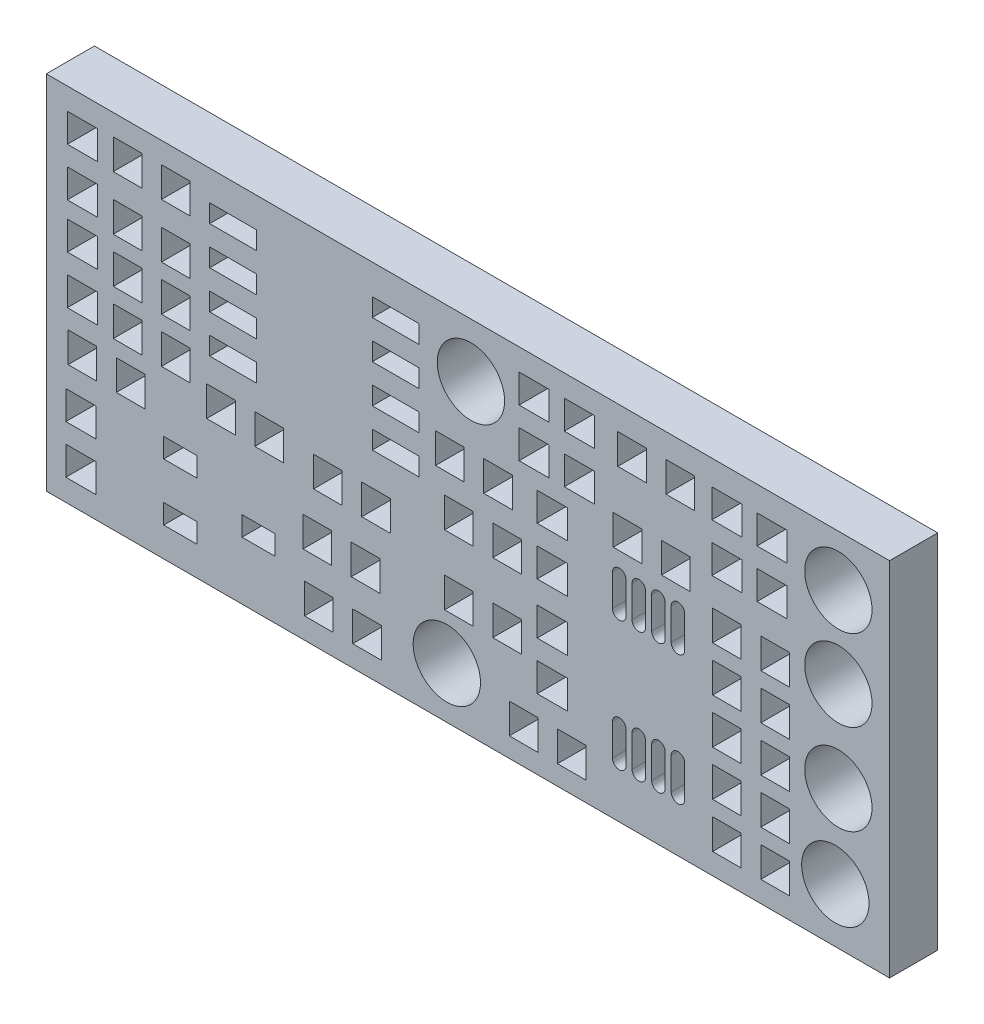
SolidWorks part; units mm, degrees
ref_plane "Plan de face" through (0, 0, 0) normal (0, 0, 1) x (1, 0, 0)
ref_plane "Plan de dessus" through (0, 0, 0) normal (0, 1, 0) x (1, 0, 0)
ref_plane "Plan de droite" through (0, 0, 0) normal (1, 0, 0) x (0, 0, -1)
sketch "Model" plane through (0, 0, 0) normal (0, 0, 1) x (1, 0, 0)
  line L0 (3.9, 2.875) -> (3.9, 3.525)
  line L1 (3.9, 3.525) -> (5, 3.525)
  line L2 (5, 3.525) -> (5, 2.875)
  line L3 (5, 2.875) -> (3.9, 2.875)
  line L4 (3.9, 0.975) -> (3.9, 1.625)
  line L5 (3.9, 1.625) -> (5, 1.625)
  line L6 (5, 1.625) -> (5, 0.975)
  line L7 (5, 0.975) -> (3.9, 0.975)
  line L8 (6.5, 1.925) -> (6.5, 2.575)
  line L9 (6.5, 2.575) -> (7.6, 2.575)
  line L10 (7.6, 2.575) -> (7.6, 1.925)
  line L11 (7.6, 1.925) -> (6.5, 1.925)
  line L12 (19.25, 2.775) -> (19.25, 1.725)
  line L13 (18.8, 1.725) -> (18.8, 2.775)
  line L14 (19.9, 2.775) -> (19.9, 1.725)
  line L15 (19.45, 1.725) -> (19.45, 2.775)
  line L16 (20.55, 2.775) -> (20.55, 1.725)
  line L17 (20.1, 1.725) -> (20.1, 2.775)
  line L18 (21.2, 2.775) -> (21.2, 1.725)
  line L19 (20.75, 1.725) -> (20.75, 2.775)
  line L20 (21.2, 7.075) -> (21.2, 6.025)
  line L21 (20.75, 6.025) -> (20.75, 7.075)
  line L22 (20.55, 7.075) -> (20.55, 6.025)
  line L23 (20.1, 6.025) -> (20.1, 7.075)
  line L24 (19.9, 7.075) -> (19.9, 6.025)
  line L25 (19.45, 6.025) -> (19.45, 7.075)
  line L26 (19.25, 7.075) -> (19.25, 6.025)
  line L27 (18.8, 6.025) -> (18.8, 7.075)
  line L28 (12.375, 7.195) -> (12.375, 6.595)
  line L29 (12.375, 6.595) -> (10.825, 6.595)
  line L30 (10.825, 6.595) -> (10.825, 7.195)
  line L31 (10.825, 7.195) -> (12.375, 7.195)
  line L32 (12.375, 8.465) -> (12.375, 7.865)
  line L33 (12.375, 7.865) -> (10.825, 7.865)
  line L34 (10.825, 7.865) -> (10.825, 8.465)
  line L35 (10.825, 8.465) -> (12.375, 8.465)
  line L36 (12.375, 9.735) -> (12.375, 9.135)
  line L37 (12.375, 9.135) -> (10.825, 9.135)
  line L38 (10.825, 9.135) -> (10.825, 9.735)
  line L39 (10.825, 9.735) -> (12.375, 9.735)
  line L40 (12.375, 11.005) -> (12.375, 10.405)
  line L41 (12.375, 10.405) -> (10.825, 10.405)
  line L42 (10.825, 10.405) -> (10.825, 11.005)
  line L43 (10.825, 11.005) -> (12.375, 11.005)
  line L44 (6.975, 11.005) -> (6.975, 10.405)
  line L45 (6.975, 10.405) -> (5.425, 10.405)
  line L46 (5.425, 10.405) -> (5.425, 11.005)
  line L47 (5.425, 11.005) -> (6.975, 11.005)
  line L48 (6.975, 9.735) -> (6.975, 9.135)
  line L49 (6.975, 9.135) -> (5.425, 9.135)
  line L50 (5.425, 9.135) -> (5.425, 9.735)
  line L51 (5.425, 9.735) -> (6.975, 9.735)
  line L52 (6.975, 8.465) -> (6.975, 7.865)
  line L53 (6.975, 7.865) -> (5.425, 7.865)
  line L54 (5.425, 7.865) -> (5.425, 8.465)
  line L55 (5.425, 8.465) -> (6.975, 8.465)
  line L56 (6.975, 7.195) -> (6.975, 6.595)
  line L57 (6.975, 6.595) -> (5.425, 6.595)
  line L58 (5.425, 6.595) -> (5.425, 7.195)
  line L59 (5.425, 7.195) -> (6.975, 7.195)
  line L60 (20.575, 11.2) -> (21.525, 11.2)
  line L61 (21.525, 11.2) -> (21.525, 10.2)
  line L62 (21.525, 10.2) -> (20.575, 10.2)
  line L63 (20.575, 10.2) -> (20.575, 11.2)
  line L64 (18.975, 11.2) -> (19.925, 11.2)
  line L65 (19.925, 11.2) -> (19.925, 10.2)
  line L66 (19.925, 10.2) -> (18.975, 10.2)
  line L67 (18.975, 10.2) -> (18.975, 11.2)
  line L68 (23.075, 5.2) -> (22.125, 5.2)
  line L69 (22.125, 5.2) -> (22.125, 6.2)
  line L70 (22.125, 6.2) -> (23.075, 6.2)
  line L71 (23.075, 6.2) -> (23.075, 5.2)
  line L72 (24.675, 5.2) -> (23.725, 5.2)
  line L73 (23.725, 5.2) -> (23.725, 6.2)
  line L74 (23.725, 6.2) -> (24.675, 6.2)
  line L75 (24.675, 6.2) -> (24.675, 5.2)
  line L76 (16.325, 0.65) -> (15.375, 0.65)
  line L77 (15.375, 0.65) -> (15.375, 1.65)
  line L78 (15.375, 1.65) -> (16.325, 1.65)
  line L79 (16.325, 1.65) -> (16.325, 0.65)
  line L80 (17.925, 0.65) -> (16.975, 0.65)
  line L81 (16.975, 0.65) -> (16.975, 1.65)
  line L82 (16.975, 1.65) -> (17.925, 1.65)
  line L83 (17.925, 1.65) -> (17.925, 0.65)
  line L84 (17.3, 6.575) -> (17.3, 5.625)
  line L85 (17.3, 5.625) -> (16.3, 5.625)
  line L86 (16.3, 5.625) -> (16.3, 6.575)
  line L87 (16.3, 6.575) -> (17.3, 6.575)
  line L88 (17.3, 8.175) -> (17.3, 7.225)
  line L89 (17.3, 7.225) -> (16.3, 7.225)
  line L90 (16.3, 7.225) -> (16.3, 8.175)
  line L91 (16.3, 8.175) -> (17.3, 8.175)
  line L92 (16.3, 3.925) -> (16.3, 4.875)
  line L93 (16.3, 4.875) -> (17.3, 4.875)
  line L94 (17.3, 4.875) -> (17.3, 3.925)
  line L95 (17.3, 3.925) -> (16.3, 3.925)
  line L96 (16.3, 2.325) -> (16.3, 3.275)
  line L97 (16.3, 3.275) -> (17.3, 3.275)
  line L98 (17.3, 3.275) -> (17.3, 2.325)
  line L99 (17.3, 2.325) -> (16.3, 2.325)
  line L100 (19.775, 7.8) -> (18.825, 7.8)
  line L101 (18.825, 7.8) -> (18.825, 8.8)
  line L102 (18.825, 8.8) -> (19.775, 8.8)
  line L103 (19.775, 8.8) -> (19.775, 7.8)
  line L104 (21.375, 7.8) -> (20.425, 7.8)
  line L105 (20.425, 7.8) -> (20.425, 8.8)
  line L106 (20.425, 8.8) -> (21.375, 8.8)
  line L107 (21.375, 8.8) -> (21.375, 7.8)
  line L108 (23.725, 7.7) -> (24.675, 7.7)
  line L109 (24.675, 7.7) -> (24.675, 6.7)
  line L110 (24.675, 6.7) -> (23.725, 6.7)
  line L111 (23.725, 6.7) -> (23.725, 7.7)
  line L112 (22.125, 7.7) -> (23.075, 7.7)
  line L113 (23.075, 7.7) -> (23.075, 6.7)
  line L114 (23.075, 6.7) -> (22.125, 6.7)
  line L115 (22.125, 6.7) -> (22.125, 7.7)
  line L116 (14.825, 6.5) -> (15.775, 6.5)
  line L117 (15.775, 6.5) -> (15.775, 5.5)
  line L118 (15.775, 5.5) -> (14.825, 5.5)
  line L119 (14.825, 5.5) -> (14.825, 6.5)
  line L120 (13.225, 6.5) -> (14.175, 6.5)
  line L121 (14.175, 6.5) -> (14.175, 5.5)
  line L122 (14.175, 5.5) -> (13.225, 5.5)
  line L123 (13.225, 5.5) -> (13.225, 6.5)
  line L124 (14.825, 4.2) -> (15.775, 4.2)
  line L125 (15.775, 4.2) -> (15.775, 3.2)
  line L126 (15.775, 3.2) -> (14.825, 3.2)
  line L127 (14.825, 3.2) -> (14.825, 4.2)
  line L128 (13.225, 4.2) -> (14.175, 4.2)
  line L129 (14.175, 4.2) -> (14.175, 3.2)
  line L130 (14.175, 3.2) -> (13.225, 3.2)
  line L131 (13.225, 3.2) -> (13.225, 4.2)
  line L132 (23.075, 3.7) -> (22.125, 3.7)
  line L133 (22.125, 3.7) -> (22.125, 4.7)
  line L134 (22.125, 4.7) -> (23.075, 4.7)
  line L135 (23.075, 4.7) -> (23.075, 3.7)
  line L136 (24.675, 3.7) -> (23.725, 3.7)
  line L137 (23.725, 3.7) -> (23.725, 4.7)
  line L138 (23.725, 4.7) -> (24.675, 4.7)
  line L139 (24.675, 4.7) -> (24.675, 3.7)
  line L140 (23.075, 2.2) -> (22.125, 2.2)
  line L141 (22.125, 2.2) -> (22.125, 3.2)
  line L142 (22.125, 3.2) -> (23.075, 3.2)
  line L143 (23.075, 3.2) -> (23.075, 2.2)
  line L144 (24.675, 2.2) -> (23.725, 2.2)
  line L145 (23.725, 2.2) -> (23.725, 3.2)
  line L146 (23.725, 3.2) -> (24.675, 3.2)
  line L147 (24.675, 3.2) -> (24.675, 2.2)
  line L148 (23.725, 1.7) -> (24.675, 1.7)
  line L149 (24.675, 1.7) -> (24.675, 0.7)
  line L150 (24.675, 0.7) -> (23.725, 0.7)
  line L151 (23.725, 0.7) -> (23.725, 1.7)
  line L152 (22.125, 1.7) -> (23.075, 1.7)
  line L153 (23.075, 1.7) -> (23.075, 0.7)
  line L154 (23.075, 0.7) -> (22.125, 0.7)
  line L155 (22.125, 0.7) -> (22.125, 1.7)
  line L156 (18.2, 9.675) -> (18.2, 8.725)
  line L157 (18.2, 8.725) -> (17.2, 8.725)
  line L158 (17.2, 8.725) -> (17.2, 9.675)
  line L159 (17.2, 9.675) -> (18.2, 9.675)
  line L160 (18.2, 11.275) -> (18.2, 10.325)
  line L161 (18.2, 10.325) -> (17.2, 10.325)
  line L162 (17.2, 10.325) -> (17.2, 11.275)
  line L163 (17.2, 11.275) -> (18.2, 11.275)
  line L164 (23.1, 9.575) -> (23.1, 8.625)
  line L165 (23.1, 8.625) -> (22.1, 8.625)
  line L166 (22.1, 8.625) -> (22.1, 9.575)
  line L167 (22.1, 9.575) -> (23.1, 9.575)
  line L168 (23.1, 11.175) -> (23.1, 10.225)
  line L169 (23.1, 10.225) -> (22.1, 10.225)
  line L170 (22.1, 10.225) -> (22.1, 11.175)
  line L171 (22.1, 11.175) -> (23.1, 11.175)
  line L172 (23.6, 10.225) -> (23.6, 11.175)
  line L173 (23.6, 11.175) -> (24.6, 11.175)
  line L174 (24.6, 11.175) -> (24.6, 10.225)
  line L175 (24.6, 10.225) -> (23.6, 10.225)
  line L176 (23.6, 8.625) -> (23.6, 9.575)
  line L177 (23.6, 9.575) -> (24.6, 9.575)
  line L178 (24.6, 9.575) -> (24.6, 8.625)
  line L179 (24.6, 8.625) -> (23.6, 8.625)
  line L180 (1.7, 9.675) -> (1.7, 8.725)
  line L181 (1.7, 8.725) -> (0.7, 8.725)
  line L182 (0.7, 8.725) -> (0.7, 9.675)
  line L183 (0.7, 9.675) -> (1.7, 9.675)
  line L184 (1.7, 11.275) -> (1.7, 10.325)
  line L185 (1.7, 10.325) -> (0.7, 10.325)
  line L186 (0.7, 10.325) -> (0.7, 11.275)
  line L187 (0.7, 11.275) -> (1.7, 11.275)
  line L188 (15.7, 10.325) -> (15.7, 11.275)
  line L189 (15.7, 11.275) -> (16.7, 11.275)
  line L190 (16.7, 11.275) -> (16.7, 10.325)
  line L191 (16.7, 10.325) -> (15.7, 10.325)
  line L192 (15.7, 8.725) -> (15.7, 9.675)
  line L193 (15.7, 9.675) -> (16.7, 9.675)
  line L194 (16.7, 9.675) -> (16.7, 8.725)
  line L195 (16.7, 8.725) -> (15.7, 8.725)
  line L196 (0.7, 7.225) -> (0.7, 8.175)
  line L197 (0.7, 8.175) -> (1.7, 8.175)
  line L198 (1.7, 8.175) -> (1.7, 7.225)
  line L199 (1.7, 7.225) -> (0.7, 7.225)
  line L200 (0.7, 5.625) -> (0.7, 6.575)
  line L201 (0.7, 6.575) -> (1.7, 6.575)
  line L202 (1.7, 6.575) -> (1.7, 5.625)
  line L203 (1.7, 5.625) -> (0.7, 5.625)
  line L204 (10.175, 1.7) -> (11.125, 1.7)
  line L205 (11.125, 1.7) -> (11.125, 0.7)
  line L206 (11.125, 0.7) -> (10.175, 0.7)
  line L207 (10.175, 0.7) -> (10.175, 1.7)
  line L208 (8.575, 1.7) -> (9.525, 1.7)
  line L209 (9.525, 1.7) -> (9.525, 0.7)
  line L210 (9.525, 0.7) -> (8.575, 0.7)
  line L211 (8.575, 0.7) -> (8.575, 1.7)
  line L212 (3.825, 11.3) -> (4.775, 11.3)
  line L213 (4.775, 11.3) -> (4.775, 10.3)
  line L214 (4.775, 10.3) -> (3.825, 10.3)
  line L215 (3.825, 10.3) -> (3.825, 11.3)
  line L216 (2.225, 11.3) -> (3.175, 11.3)
  line L217 (3.175, 11.3) -> (3.175, 10.3)
  line L218 (3.175, 10.3) -> (2.225, 10.3)
  line L219 (2.225, 10.3) -> (2.225, 11.3)
  line L220 (1.65, 1.675) -> (1.65, 0.725)
  line L221 (1.65, 0.725) -> (0.65, 0.725)
  line L222 (0.65, 0.725) -> (0.65, 1.675)
  line L223 (0.65, 1.675) -> (1.65, 1.675)
  line L224 (1.65, 3.275) -> (1.65, 2.325)
  line L225 (1.65, 2.325) -> (0.65, 2.325)
  line L226 (0.65, 2.325) -> (0.65, 3.275)
  line L227 (0.65, 3.275) -> (1.65, 3.275)
  line L228 (14.525, 8.2) -> (15.475, 8.2)
  line L229 (15.475, 8.2) -> (15.475, 7.2)
  line L230 (15.475, 7.2) -> (14.525, 7.2)
  line L231 (14.525, 7.2) -> (14.525, 8.2)
  line L232 (12.925, 8.2) -> (13.875, 8.2)
  line L233 (13.875, 8.2) -> (13.875, 7.2)
  line L234 (13.875, 7.2) -> (12.925, 7.2)
  line L235 (12.925, 7.2) -> (12.925, 8.2)
  line L236 (6.275, 4.75) -> (5.325, 4.75)
  line L237 (5.325, 4.75) -> (5.325, 5.75)
  line L238 (5.325, 5.75) -> (6.275, 5.75)
  line L239 (6.275, 5.75) -> (6.275, 4.75)
  line L240 (7.875, 4.75) -> (6.925, 4.75)
  line L241 (6.925, 4.75) -> (6.925, 5.75)
  line L242 (6.925, 5.75) -> (7.875, 5.75)
  line L243 (7.875, 5.75) -> (7.875, 4.75)
  line L244 (2.325, 5) -> (3.275, 5)
  line L245 (3.275, 5) -> (3.275, 4)
  line L246 (3.275, 4) -> (2.325, 4)
  line L247 (2.325, 4) -> (2.325, 5)
  line L248 (0.725, 5) -> (1.675, 5)
  line L249 (1.675, 5) -> (1.675, 4)
  line L250 (1.675, 4) -> (0.725, 4)
  line L251 (0.725, 4) -> (0.725, 5)
  line L252 (10.125, 3.6) -> (11.075, 3.6)
  line L253 (11.075, 3.6) -> (11.075, 2.6)
  line L254 (11.075, 2.6) -> (10.125, 2.6)
  line L255 (10.125, 2.6) -> (10.125, 3.6)
  line L256 (8.525, 3.6) -> (9.475, 3.6)
  line L257 (9.475, 3.6) -> (9.475, 2.6)
  line L258 (9.475, 2.6) -> (8.525, 2.6)
  line L259 (8.525, 2.6) -> (8.525, 3.6)
  line L260 (9.825, 4.5) -> (8.875, 4.5)
  line L261 (8.875, 4.5) -> (8.875, 5.5)
  line L262 (8.875, 5.5) -> (9.825, 5.5)
  line L263 (9.825, 5.5) -> (9.825, 4.5)
  line L264 (11.425, 4.5) -> (10.475, 4.5)
  line L265 (10.475, 4.5) -> (10.475, 5.5)
  line L266 (10.475, 5.5) -> (11.425, 5.5)
  line L267 (11.425, 5.5) -> (11.425, 4.5)
  line L268 (3.175, 7) -> (2.225, 7)
  line L269 (2.225, 7) -> (2.225, 8)
  line L270 (2.225, 8) -> (3.175, 8)
  line L271 (3.175, 8) -> (3.175, 7)
  line L272 (4.775, 7) -> (3.825, 7)
  line L273 (3.825, 7) -> (3.825, 8)
  line L274 (3.825, 8) -> (4.775, 8)
  line L275 (4.775, 8) -> (4.775, 7)
  line L276 (3.175, 8.5) -> (2.225, 8.5)
  line L277 (2.225, 8.5) -> (2.225, 9.5)
  line L278 (2.225, 9.5) -> (3.175, 9.5)
  line L279 (3.175, 9.5) -> (3.175, 8.5)
  line L280 (4.775, 8.5) -> (3.825, 8.5)
  line L281 (3.825, 8.5) -> (3.825, 9.5)
  line L282 (3.825, 9.5) -> (4.775, 9.5)
  line L283 (4.775, 9.5) -> (4.775, 8.5)
  line L284 (3.825, 6.5) -> (4.775, 6.5)
  line L285 (4.775, 6.5) -> (4.775, 5.5)
  line L286 (4.775, 5.5) -> (3.825, 5.5)
  line L287 (3.825, 5.5) -> (3.825, 6.5)
  line L288 (2.225, 6.5) -> (3.175, 6.5)
  line L289 (3.175, 6.5) -> (3.175, 5.5)
  line L290 (3.175, 5.5) -> (2.225, 5.5)
  line L291 (2.225, 5.5) -> (2.225, 6.5)
  line L292 (0, 0) -> (0, 12)
  line L293 (0, 12) -> (28, 12)
  line L294 (28, 12) -> (28, 0)
  line L295 (28, 0) -> (0, 0)
  circle A0 centre (26.3, 10.3) radius 1.1176
  circle A1 centre (26.3, 10.3) radius 1.1176
  circle A2 centre (26.3, 7.6) radius 1.1176
  circle A3 centre (26.3, 7.6) radius 1.1176
  circle A4 centre (26.2, 1.8) radius 1.1176
  circle A5 centre (26.2, 1.8) radius 1.1176
  circle A6 centre (26.3, 4.6) radius 1.1176
  circle A7 centre (26.3, 4.6) radius 1.1176
  circle A8 centre (13.3, 1.7) radius 1.1176
  circle A9 centre (13.3, 1.7) radius 1.1176
  circle A10 centre (14.1, 10.2) radius 1.1176
  circle A11 centre (14.1, 10.2) radius 1.1176
  arc A12 (18.8, 1.725) -> (19.25, 1.725) centre (19.025, 1.725) ccw
  arc A13 (19.25, 2.775) -> (18.8, 2.775) centre (19.025, 2.775) ccw
  arc A14 (19.45, 1.725) -> (19.9, 1.725) centre (19.675, 1.725) ccw
  arc A15 (19.9, 2.775) -> (19.45, 2.775) centre (19.675, 2.775) ccw
  arc A16 (20.1, 1.725) -> (20.55, 1.725) centre (20.325, 1.725) ccw
  arc A17 (20.55, 2.775) -> (20.1, 2.775) centre (20.325, 2.775) ccw
  arc A18 (20.75, 1.725) -> (21.2, 1.725) centre (20.975, 1.725) ccw
  arc A19 (21.2, 2.775) -> (20.75, 2.775) centre (20.975, 2.775) ccw
  arc A20 (20.75, 6.025) -> (21.2, 6.025) centre (20.975, 6.025) ccw
  arc A21 (21.2, 7.075) -> (20.75, 7.075) centre (20.975, 7.075) ccw
  arc A22 (20.1, 6.025) -> (20.55, 6.025) centre (20.325, 6.025) ccw
  arc A23 (20.55, 7.075) -> (20.1, 7.075) centre (20.325, 7.075) ccw
  arc A24 (19.45, 6.025) -> (19.9, 6.025) centre (19.675, 6.025) ccw
  arc A25 (19.9, 7.075) -> (19.45, 7.075) centre (19.675, 7.075) ccw
  arc A26 (18.8, 6.025) -> (19.25, 6.025) centre (19.025, 6.025) ccw
  arc A27 (19.25, 7.075) -> (18.8, 7.075) centre (19.025, 7.075) ccw
extrude "Boss.-Extru.1" add sketch "Model" along normal blind 1.6 contours L295 L294 L293 L292 A27 L26 A26 L27 A25 L24 A24 L25 A23 L22 A22 L23 A21 L20 A20 L21 A19 L18 A18 L19 A17 L16 A16 L17 A15 L14 A14 L15 A13 L12 A12 L13 A10 A8 A6 region at (0.3046, 6, 0)
